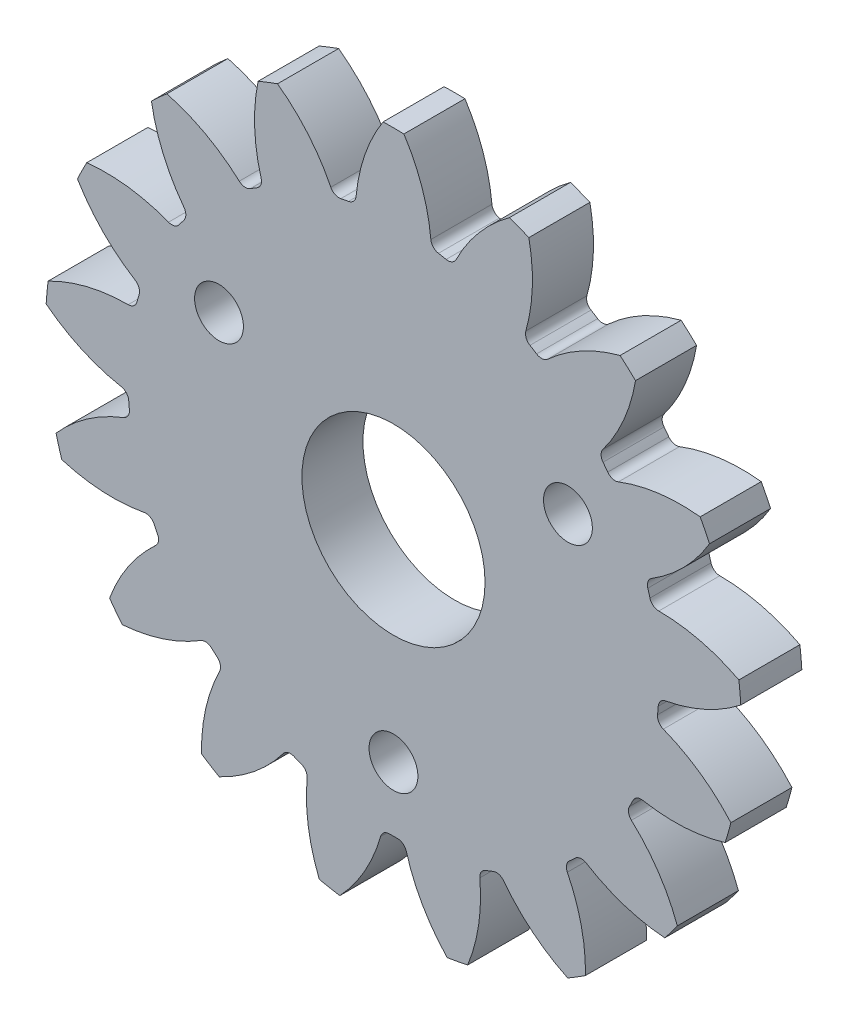
SolidWorks part; units mm, degrees
ref_plane "정면" through (0, 0, 0) normal (0, 0, 1) x (1, 0, 0)
ref_plane "윗면" through (0, 0, 0) normal (0, 1, 0) x (1, 0, 0)
ref_plane "우측면" through (0, 0, 0) normal (1, 0, 0) x (0, 0, -1)
sketch "스케치1" plane through (0, 0, 0) normal (0, 0, 1) x (1, 0, 0)
  line L0 (0, 32.6911) -> (0, -34.4172) construction
  line L1 (-2.355, 25.391) -> (-2.355, -34.4172) construction
  line L2 (-0.855, 28.4872) -> (-0.855, -34.4172) construction
  line L3 (-3.105, 21.5272) -> (-3.105, -34.4172) construction
  line L4 (-0.855, 32.6911) -> (-0.855, -34.4172) construction
  line L5 (-2.355, 32.6911) -> (-2.355, -34.4172) construction
  line L6 (-3.105, 32.6911) -> (-3.105, -34.4172) construction
  circle A0 centre (0, 0) radius 25.5 construction
  circle A1 centre (0, 0) radius 21.75
  circle A2 centre (0, 0) radius 28.5
  arc A3 (-3.105, 21.5272) -> (-0.855, 28.4872) centre (11.132, 20.7684) cw
  arc A4 (3.105, 21.5272) -> (0.855, 28.4872) centre (-11.132, 20.7684) ccw
  dimension "D1" = 51
  dimension "D2" = 43.5
  dimension "D3" = 57
  dimension "D4" = 2.355
  dimension "D5" = 1.5
  dimension "D6" = 0.75
extrude "보스-돌출1" add sketch "스케치1" along normal blind 5 contours A1
extrude "보스-돌출2" add sketch "스케치1<3>" along normal blind 5 contours A1 A4 A2 A3 region at (0, 24.5376, 0)
sketch "스케치1<3>" plane through (0, 0, 0) normal (0, 0, 1) x (1, 0, 0) same geometry as "스케치1"
fillet "필렛1" radius 0.75 2 edges at (3.105, 21.5272, 2.5) (-3.105, 21.5272, 2.5)
sketch "스케치2" plane through (0, 0, 5) normal (0, 0, 1) x (1, 0, 0)
  circle A0 centre (0, 0) radius 7.5
  circle A1 centre (0, 0) radius 12.5
  circle A2 centre (0, 0) radius 16.5 construction
  circle A3 centre (0, -16.5) radius 2
  circle A6 centre (-14.2894, 8.25) radius 2
  circle A7 centre (14.2894, 8.25) radius 2
  point P16 (0, 0)
  dimension "D1" = 15
  dimension "D4" = 4
  dimension "D3" = 4
  dimension "D2" = 5
  dimension "D5" = 3
extrude "컷-돌출1" cut sketch "스케치2" against normal up to next contours A0 | A6 | A7 | A3 | A0 region at (0, 0, 5) region at (0, -16.5, 5) region at (-14.2894, 8.25, 5) region at (14.2894, 8.25, 5)
pattern_circular "원형 패턴1" count 17 over 360 about axis through (0, 0, -0.001) along (0, 0, 1) of "보스-돌출2", "필렛1" reverse direction yes
